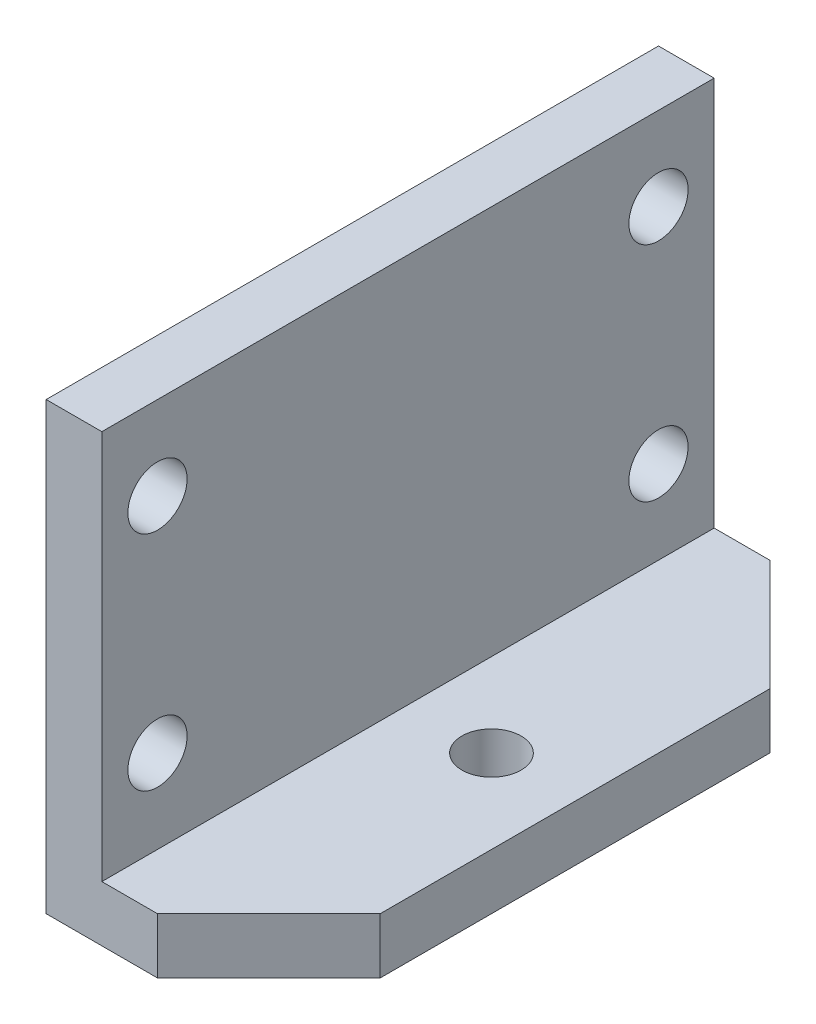
SolidWorks part; units mm, degrees
ref_plane "Front" through (0, 0, 0) normal (0, 0, 1) x (1, 0, 0)
ref_plane "Top" through (0, 0, 0) normal (0, 1, 0) x (1, 0, 0)
ref_plane "Right" through (0, 0, 0) normal (1, 0, 0) x (0, 0, -1)
sketch "Sketch1" plane through (0, 0, 0) normal (0, 0, 1) x (1, 0, 0)
  line L0 (0, 50.8) -> (0, 0)
  line L1 (0, -50) -> (0, 50) construction
  line L2 (0, 0) -> (25.4, 0)
  line L3 (50, 0) -> (-50, 0) construction
  line L4 (25.4, 0) -> (25.4, 6.35)
  line L5 (25.4, 6.35) -> (6.35, 6.35)
  line L6 (6.35, 6.35) -> (6.35, 50.8)
  line L7 (6.35, 50.8) -> (0, 50.8)
  dimension "D1" = 6.35
  dimension "D2" = 50.8
  dimension "D3" = 25.4
extrude "Boss-Extrude1" add sketch "Sketch1" along normal mid plane 69.85
sketch "Sketch2" plane through (0, 0, 0) normal (-1, 0, 0) x (0, 0, 1)
  line L0 (-34.925, 15.875) -> (-28.575, 15.875) construction
  line L1 (-34.925, 50.8) -> (-34.925, 0) construction
  line L2 (-28.575, 15.875) -> (28.575, 15.875) construction
  line L3 (28.575, 15.875) -> (34.925, 15.875) construction
  line L4 (34.925, 50.8) -> (34.925, 0) construction
  line L5 (34.925, 0) -> (-34.925, 0) construction
  line L6 (-34.925, 41.275) -> (-28.575, 41.275) construction
  line L7 (-28.575, 41.275) -> (28.575, 41.275) construction
  line L8 (28.575, 41.275) -> (34.925, 41.275) construction
  line L9 (34.925, 50.8) -> (-34.925, 50.8) construction
  dimension "D1" = 57.15
  dimension "D2" = 15.875
  dimension "D3" = 9.525
hole_wizard "1/4 Clearance Hole1" positions "Sketch4" profile "Sketch3" hole size "1/4" standard "ANSI Inch" end condition through all
sketch "Sketch4" plane through (0, 0, 0) normal (-1, 0, 0) x (0, 0, 1)
  point P0 (-28.575, 15.875)
  point P3 (28.575, 15.875)
  point P6 (-28.575, 41.275)
  point P9 (28.575, 41.275)
sketch "Sketch3" plane through (0, 15.875, -28.575) normal (0, 1, 0) x (0, 0, 1)
  line L0 (0, 0) -> (0, 25.4)
  line L1 (0, 25.4) -> (3.3782, 25.4)
  line L2 (3.3782, 25.4) -> (3.3782, 0)
  line L5 (3.3782, 0) -> (0, 0)
  line L11 (0, -6.35) -> (0, 107.95) construction
  dimension "Thru Hole Dia." = 6.7564
  dimension "Thru Hole Depth" = 25.4
sketch "Sketch5" plane through (0, 6.35, 0) normal (0, 1, 0) x (1, 0, 0)
  line L0 (6.35, 0) -> (15.875, 0) construction
  line L1 (6.35, -34.925) -> (6.35, 34.925) construction
  dimension "D1" = 9.525
hole_wizard "1/4 Clearance Hole2" positions "Sketch7" profile "Sketch6" hole size "1/4" standard "ANSI Inch" end condition through all
sketch "Sketch7" plane through (0, 6.35, 0) normal (0, 1, 0) x (1, 0, 0)
  point P0 (15.875, 0)
sketch "Sketch6" plane through (15.875, 6.35, 0) normal (1, 0, 0) x (0, 0, 1)
  line L0 (0, 0) -> (0, 6.35)
  line L1 (0, 6.35) -> (3.3782, 6.35)
  line L2 (3.3782, 6.35) -> (3.3782, 0)
  line L5 (3.3782, 0) -> (0, 0)
  line L11 (0, -6.35) -> (0, 107.95) construction
  dimension "Thru Hole Dia." = 6.7564
  dimension "Thru Hole Depth" = 6.35
chamfer "Chamfer1" distance 12.7 angle 45 2 edges at (25.4, 3.175, -34.925) (25.4, 3.175, 34.925)
